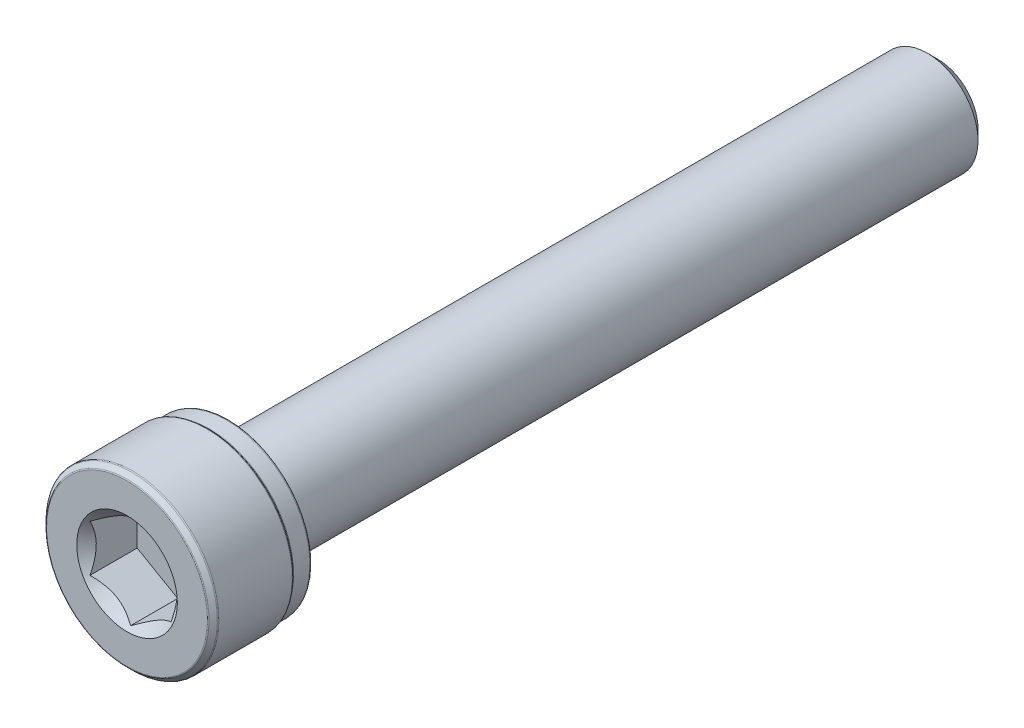
SolidWorks part; units mm, degrees
ref_plane "Front Plane" through (0, 0, 0) normal (0, 0, 1) x (1, 0, 0)
ref_plane "Top Plane" through (0, 0, 0) normal (0, 1, 0) x (1, 0, 0)
ref_plane "Right Plane" through (0, 0, 0) normal (1, 0, 0) x (0, 0, -1)
sketch "Sketch1" plane through (0, 0, 0) normal (1, 0, 0) x (0, 0, -1)
  line L0 (-20, 0) -> (20, 0) construction
  line L1 (20, 0) -> (20, 1.9804) construction
  line L2 (20, 1.9804) -> (19.4804, 2.5) construction
  line L3 (19.4804, 2.5) -> (19.4, 2.5) construction
  line L4 (19.4, 2.5) -> (-15, 2.5) construction
  line L5 (-15, 2.5) -> (-15, 4.25) construction
  line L6 (-15, 4.25) -> (-20, 4.25) construction
  line L7 (-20, 4.25) -> (-20, 0) construction
  line L8 (20, 1.9804) -> (20, 2.5) construction
  line L9 (19.95, 2.5866) -> (20.35, 1.8938) construction
  line L10 (20.35, 1.8938) -> (20.75, 2.5866) construction
  line L11 (20.75, 2.5866) -> (19.95, 2.5866) construction
  line L12 (20.35, 2.5866) -> (20.35, 2.5) construction
  line L13 (20.35, 1.8938) -> (20.35, 1.9804) construction
  line L14 (20.3, 1.9804) -> (20.4, 1.9804) construction
  line L15 (20, 2.5) -> (20.7, 2.5) construction
  line L16 (19.975, 2.5433) -> (20.725, 2.5433) construction
  line L17 (20, 0) -> (20, -2.5) construction
  line L18 (-15.25, 4.25) -> (-15, 4) construction
  line L19 (-19.75, 4.25) -> (-20, 4) construction
  line L20 (-15, 2.5) -> (-15, 0) construction
  line L21 (-15, 1.25) -> (-3.3333, 1.25) construction
  line L22 (-3.3333, 1.25) -> (8.3333, 1.25) construction
  line L23 (8.3333, 1.25) -> (20, 1.25) construction
  line L24 (-3.3333, 1.25) -> (-3.3333, 2.5) construction
  line L25 (-3.3333, 2.5) -> (-3.3333, 4.25) construction
  line L26 (8.3333, 1.25) -> (8.3333, 4.25) construction
  point P0 (-20, 2)
  point P3 (18, 2.5)
  point P4 (0, 0)
  point P18 (8.3333, 2.5)
  point P22 (20.35, 1.9804)
  point P24 (19.4, 2.5)
  point P25 (20.35, 2.5)
  point P28 (20.35, 2.5433)
  point P29 (18, -2.5)
  point P30 (-3.3333, 2.5)
  point P31 (-17.5, 4.25)
  point P37 (-15.875, 4.25)
  point P38 (-19.625, 4.25)
  point P45 (-3.3333, 1.25)
  point P46 (8.3333, 1.25)
  dimension "D1" = 45
  dimension "D2" = 0.1
  dimension "D7" = 0.25
  dimension "D8" = 0.25
  dimension "D9" = 0.25
  dimension "D10" = 0.125
  dimension "D11" = 0.625
  dimension "Drive Size" = 4
  dimension "Head Diameter" = 8.5
  dimension "Head Height" = 5
  dimension "Thread Pitch" = 0.8
  dimension "Thread Dia" = 5
  dimension "Length" = 35
  dimension "D12" = 0.6
  dimension "D4" = 2
  dimension "Key Engagement" = 2.5
sketch "Sketch2" plane through (0, 0, 0) normal (1, 0, 0) x (0, 0, -1)
  line L0 (-20, 0) -> (-20, 3.9676)
  line L1 (-19.7176, 4.25) -> (-16.0949, 4.25)
  line L2 (-15, 4.0188) -> (-15, 2.75)
  line L4 (19.4804, 2.5) -> (20, 1.9804)
  line L5 (20, 1.9804) -> (20, 0)
  line L6 (-15, 4.25) -> (-20, 4.25) construction
  line L7 (20, 0) -> (-20, 0)
  line L8 (-19.75, 4.25) -> (-20, 4) construction
  line L10 (-19.7729, 4.2271) -> (-19.9771, 4.0229)
  line L12 (-15.9051, 4.125) -> (-15.1063, 4.125)
  line L14 (-15.25, 4.25) -> (-15, 4) construction
  line L15 (-16.0396, 4.2271) -> (-15.9604, 4.1479)
  line L17 (-15, 2.5) -> (-15, 4.25) construction
  line L19 (-14.75, 2.5) -> (19.4804, 2.5)
  line L20 (19.4, 2.5) -> (-15, 2.5) construction
  arc A0 (-15.1063, 4.125) -> (-15, 4.0188) centre (-15.1063, 4.0188) cw
  arc A1 (-15, 2.75) -> (-14.75, 2.5) centre (-14.75, 2.75) ccw
  arc A2 (-19.7729, 4.2271) -> (-19.7176, 4.25) centre (-19.7176, 4.1719) cw
  arc A3 (-19.9771, 4.0229) -> (-20, 3.9676) centre (-19.9219, 3.9676) ccw
  arc A4 (-16.0396, 4.2271) -> (-16.0949, 4.25) centre (-16.0949, 4.1719) ccw
  arc A5 (-15.9604, 4.1479) -> (-15.9051, 4.125) centre (-15.9051, 4.2031) ccw
  point P22 (-15.125, 4.125)
  point P37 (-15.9375, 4.125)
  dimension "D2" = 0.1063
  dimension "D3" = 0.25
  dimension "D4" = 0.0781
  dimension "D1" = 0.9375
revolve "Revolve1" add sketch "Sketch2" angle 360 about L7
sketch "Sketch3" plane through (0, 0, 20) normal (0, 0, 1) x (1, 0, 0)
  line L1 (2, -1.1547) -> (2, 1.1547)
  line L2 (2, 1.1547) -> (0, 2.3094)
  line L3 (0, 2.3094) -> (-2, 1.1547)
  line L4 (-2, 1.1547) -> (-2, -1.1547)
  line L5 (-2, -1.1547) -> (0, -2.3094)
  line L6 (0, -2.3094) -> (2, -1.1547)
  circle A0 centre (0, 0) radius 2 construction
  circle A1 centre (0, 0) radius 4.25 construction
  circle A2 centre (0, 0) radius 4.25 construction
  circle A3 centre (0, 0) radius 2.3094 construction
  dimension "D1" = 4.6188
extrude "Cut-Extrude1" cut sketch "Sketch3" against normal up to vertex (2.5 mm away) up to point (0, 4.25, 17.5)
sketch "Sketch4" plane through (0, 0, 20) normal (0, 0, 1) x (1, 0, 0)
  circle A0 centre (0, 0) radius 2.4826
  dimension "D1" = 4.9652
extrude "Cut-Extrude2" cut sketch "Sketch4" against normal up to vertex (2.5 mm away) draft 45 up to point (0, 4.25, 17.5)
sketch "Sketch6" [suppressed] plane through (0, 0, -20) normal (0, 0, -1) x (-1, 0, 0)
  circle A0 centre (0, 0) radius 2.5
curve "Helix/Spiral1" [suppressed] pitch 0.8 height 35.8 turns 44.75
sketch "Sketch7" [suppressed] plane through (0, 0, 0) normal (1, 0, 0) x (0, 0, -1)
  line L0 (19.975, 2.5433) -> (20.725, 2.5433)
  line L1 (20.725, 2.5433) -> (20.4, 1.9804)
  line L2 (20.4, 1.9804) -> (20.3, 1.9804)
  line L3 (20.3, 1.9804) -> (19.975, 2.5433)
sweep "Cut-Sweep1" [suppressed] cut profiles "Sketch7" path "Helix/Spiral1"
sketch "Sketch8" [suppressed] plane through (0, 0, 0) normal (1, 0, 0) x (0, 0, -1)
  line L0 (-17.5, 0) -> (-17.5, 2.75)
  line L1 (-17.5, 1.1547) -> (-17.5, 2.3094) construction
  line L2 (-14.75, 2.5) -> (-14.6, 2.5)
  line L3 (-15, 2.75) -> (-17.5, 2.75)
  line L4 (-14.6, 2.5) -> (-13.1566, 0)
  line L5 (-13.1566, 0) -> (-17.5, 0)
  line L7 (-20, 0) -> (20, 0) construction
  line L8 (-15, 2.5) -> (-15, 4.25) construction
  arc A0 (-15, 2.75) -> (-14.75, 2.5) centre (-14.75, 2.75) ccw construction
  arc A1 (-15, 2.75) -> (-14.75, 2.5) centre (-14.75, 2.75) ccw
  dimension "D1" = 60
  dimension "D2" = 0.4
revolve "Revolve2" [suppressed] add sketch "Sketch8" angle 360 about L5
sketch "Sketch9" [suppressed] plane through (0, 0, 20) normal (0, 0, 1) x (1, 0, 0)
  line L0 (-0.0194, 4.1683) -> (-0.1062, 4.3622)
  line L1 (-0.1062, 4.3622) -> (0.1063, 4.3622)
  line L2 (0.1063, 4.3622) -> (0.0194, 4.1683)
  line L3 (0, 4.25) -> (0, 4) construction
  line L4 (0, 0) -> (-0.1062, 4.3622) construction
  line L5 (0.1063, 4.3622) -> (0, 0) construction
  circle A0 centre (0, 0) radius 4.125 construction
  arc A4 (-0.0194, 4.1683) -> (0.0194, 4.1683) centre (0, 4.177) ccw
  point P10 (0, 4.125)
  point P19 (0, 4.125)
  dimension "D2" = 0.0213
  dimension "D1" = 0.2125
  dimension "D3" = 2.791
extrude "Cut-Extrude3" [suppressed] cut sketch "Sketch9" against normal through all
pattern_circular "CirPattern1" [suppressed] count 80 over 360 of bodies 112
equation "\"D2@Sketch1\" = \"Thread Pitch@Sketch1\" / 8"
equation "\"D4@Helix/Spiral1\" = \"Thread Pitch@Sketch1\""
equation "\"D7@Sketch1\" = \"Head Height@Sketch1\" * .05"
equation "\"D8@Sketch1\"=\"D7@Sketch1\""
equation "\"D9@Sketch1\"=\"D7@Sketch1\""
equation "\"D10@Sketch1\"=\"D7@Sketch1\"/2"
equation "\"D11@Sketch1\"=\"D10@Sketch1\"*5"
equation "\"D4@Sketch1\"=\"Thread Pitch@Sketch1\"*2.5"
equation "\"D12@Sketch1\"=\"Thread Pitch@Sketch1\"*.75"
equation "\"D3@Helix/Spiral1\"=\"Length@Sketch1\"+\"Thread Pitch@Sketch1\""
equation "\"D1@Sketch2\"=\"Head Height@Sketch1\"*0.1875"
equation "\"D2@Sketch2\"=\"Head Diameter@Sketch1\"*0.0125"
equation "\"D3@Sketch2\"=\"Thread Dia@Sketch1\"*0.05"
equation "\"D1@Sketch9\"=\"Head Diameter@Sketch1\"*0.025"
equation "\"D2@Sketch9\"=\"D1@Sketch9\"*0.1"
equation "\"D2@Sketch8\"=\"Thread Pitch@Sketch1\"*00.5"
equation "\"D4@Sketch2\"=\"D8@Sketch1\"*0.3125"
equation "\"D1@CirPattern1\"=int ((360/\"D3@Sketch9\")*0.625)"
equation "\"D1@Sketch4\"=\"D1@Sketch3\" * 01.075"
